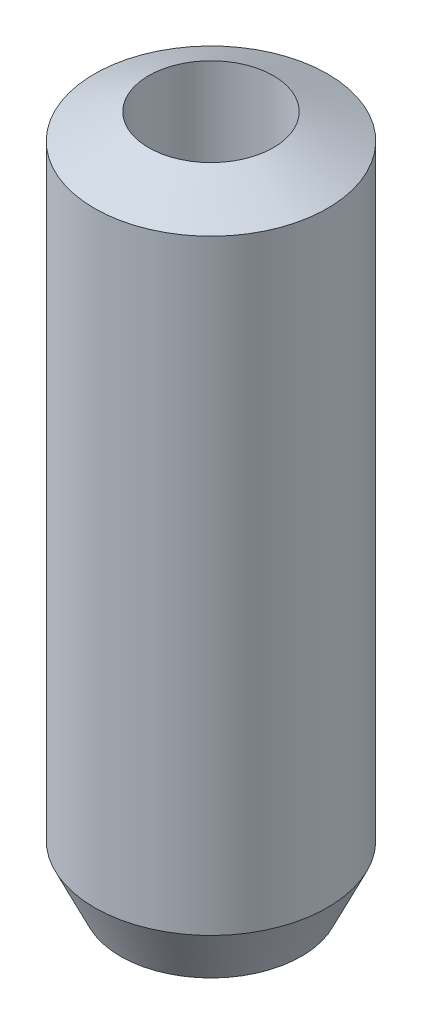
SolidWorks part; units mm, degrees
ref_plane "Front Plane" through (0, 0, 0) normal (0, 0, 1) x (1, 0, 0)
ref_plane "Top Plane" through (0, 0, 0) normal (0, 1, 0) x (1, 0, 0)
ref_plane "Right Plane" through (0, 0, 0) normal (1, 0, 0) x (0, 0, -1)
sketch "Sketch1" plane through (0, 0, 0) normal (0, 1, 0) x (1, 0, 0)
  circle A0 centre (0, 0) radius 10
  dimension "SHAFT_OD" = 20
extrude "Boss-Extrude1" add sketch "Sketch1" along normal blind 58.9362
sketch "Sketch2" plane through (0, 0, 0) normal (0, 1, 0) x (1, 0, 0)
  circle A0 centre (0, 0) radius 5.3553
  dimension "BORE_D" = 10.7107
extrude "Cut-Extrude1" cut sketch "Sketch2" along normal through all
chamfer "Chamfer1" distance 2.2313 angle 64.779 2 edges at (0, 58.9362, 10) (0, 0, 10) first distance on face at (0, 58.9362, 10) first distance on face at (0, 0, 5.3553)
